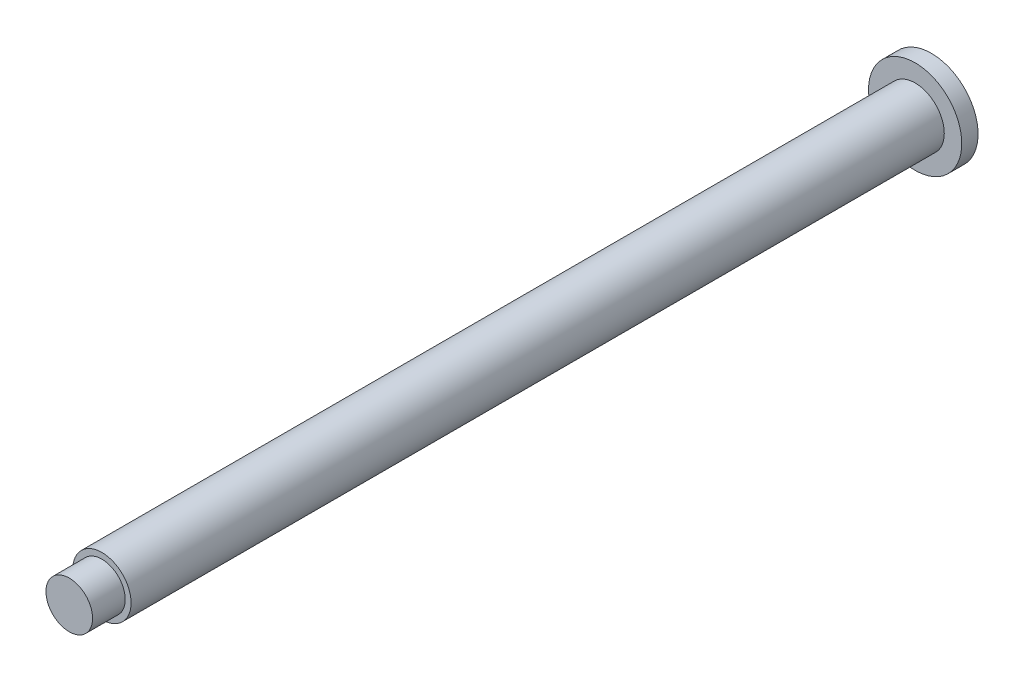
SolidWorks part; units mm, degrees
ref_plane "Front Plane" through (0, 0, 0) normal (1, 0, 0) x (0, 1, 0)
ref_plane "Top Plane" through (0, 0, 0) normal (0, 0, 1) x (0, 1, 0)
ref_plane "Right Plane" through (0, 0, 0) normal (0, 1, 0) x (-1, 0, 0)
sketch "Sketch1" plane through (0, 0, 0) normal (0, 0, 1) x (0, 1, 0)
  circle A0 centre (0, 0) radius 2.5
  dimension "D1" = 5
extrude "Boss-Extrude1" add sketch "Sketch1" along normal blind 69.75 contours A0
sketch "Sketch2" plane through (0, 0, 0) normal (0, 0, -1) x (1, 0, 0)
  circle A0 centre (0, 0) radius 4
  dimension "D1" = 8
extrude "Boss-Extrude2" add sketch "Sketch2" along normal blind 1.4
sketch "Sketch3" plane through (0, 0, -1.4) normal (0, 0, -1) x (1, 0, 0)
  circle A0 centre (0, 0) radius 2.05
  dimension "D1" = 4.1
extrude "Cut-Extrude1" cut sketch "Sketch3" against normal blind 3
sketch "Sketch4" plane through (0, 0, 69.75) normal (0, 0, 1) x (1, 0, 0)
  circle A0 centre (0, 0) radius 2
extrude "Boss-Extrude3" add sketch "Sketch4" along normal blind 2.8
equation "\"whitekey_cutout_length\"= 101.5"
equation "\"key_mount_recess_length\"=50"
equation "\"key_mount_recess_height\"=12.5"
equation "\"key_mount_recess_depth\"=1.5"
equation "\"wall_thickness\"=10"
equation "\"guide_brace_height\"=20"
equation "\"guide_brace_thickness\"=2"
equation "\"dowel_recess_depth\"=9"
equation "\"dowel_recess_offset\"=3.25"
equation "\"base_mount_height\"=40"
equation "\"base_rear_length\"=80"
equation "\"base_front_length\"=111.5"
equation "\"screw_hole_wall_offset\"=7.25"
equation "\"screw_hole_edge_inset\"=4.5"
equation "\"screw_hole_diameter\"=3.8"
equation "\"screw_head_hole_diameter\"=6.7"
equation "\"screw_nut_hole_side_len\"=3.5"
equation "\"screw_nut_recess_offset\"=0.4"
equation "\"screw_head_and_nut_recess_depth\"=2.5"
equation "\"screw_shaft_diameter\"=3.5"
equation "\"switch_board_width\"=30"
equation "\"switch_board_wall_offset\"=11.5"
equation "\"heatset_insert_hole_diameter\"=4.8"
equation "\"heatset_insert_hole_depth\"=3.8"
equation "\"front_rear_panel_width\"=23.75"
equation "\"rod_length_adj\"=0.5"
equation "\"rod_insert_length\"=2.8"
equation "\"D1@Boss-Extrude3\"=\"rod_insert_length\""
equation "\"D1@Boss-Extrude2\"=2-\"rod_length_adj\"-0.1"
equation "\"D1@Boss-Extrude1\"=\"rod_length_adj\"+69.25mm"
equation "\"switch_board_thickness\"=1.6"
equation "\"rod_diameter\"=5"
equation "\"rod_head_diameter\"=8"
equation "\"switch_black_key_mount_height\"=8"
equation "\"switch_white_key_mount_height\"=3"
equation "\"D1@Sketch1\"=\"rod_diameter\""
equation "\"D1@Sketch2\"=\"rod_head_diameter\""
equation "\"D1@Sketch3\"=\"rod_diameter\"-1+0.1"
equation "\"D1@Sketch4\"=\"rod_diameter\"-1"
